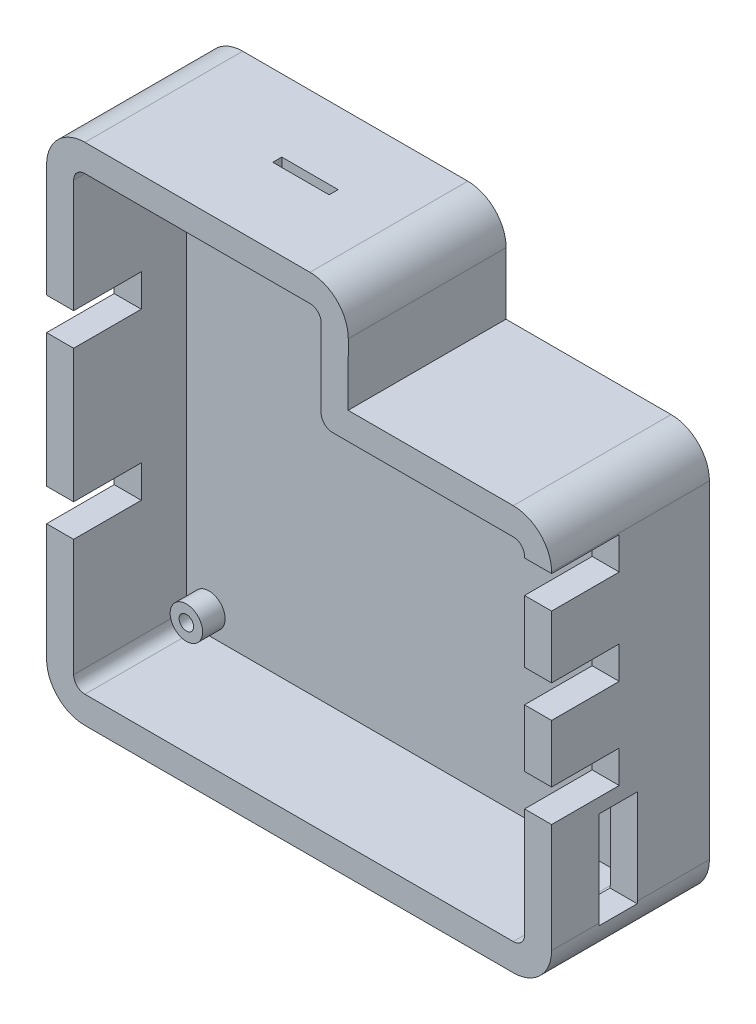
SolidWorks part; units mm, degrees
ref_plane "Front Plane" through (0, 0, 0) normal (0, 0, 1) x (1, 0, 0)
ref_plane "Top Plane" through (0, 0, 0) normal (0, 1, 0) x (1, 0, 0)
ref_plane "Right Plane" through (0, 0, 0) normal (1, 0, 0) x (0, 0, -1)
sketch "Sketch4" plane through (0, 0, 0) normal (0, 0, 1) x (1, 0, 0)
  line L0 (34.8872, 175.0129) -> (-15.0228, 175.0129)
  line L1 (-23.5228, 166.5129) -> (-23.5228, 71.5129)
  line L2 (-15.0228, 63.0129) -> (79.9772, 63.0129)
  line L3 (88.4772, 71.5129) -> (88.4772, 144.2329)
  line L4 (79.9772, 152.7329) -> (77.9872, 152.7329)
  line L5 (77.9872, 152.7329) -> (71.6372, 152.7329)
  line L6 (71.6372, 152.7329) -> (50.0472, 152.7329)
  line L7 (50.0472, 152.7329) -> (43.6972, 152.7329)
  line L8 (43.6972, 152.7329) -> (43.3553, 152.7329)
  line L9 (43.3553, 152.7329) -> (43.3872, 166.4932)
  line L20 (34.8872, 169.0129) -> (-15.0228, 169.0129)
  line L21 (-17.5228, 166.5129) -> (-17.5228, 71.5129)
  line L22 (-15.0228, 69.0129) -> (79.9772, 69.0129)
  line L23 (82.4772, 71.5129) -> (82.4772, 144.2329)
  line L24 (79.9772, 146.7329) -> (77.9872, 146.7329)
  line L25 (77.9872, 146.7329) -> (71.6372, 146.7329)
  line L26 (71.6372, 146.7329) -> (50.0472, 146.7329)
  line L27 (50.0472, 146.7329) -> (43.6972, 146.7329)
  line L28 (43.6972, 146.7329) -> (39.8872, 146.7329)
  line L29 (37.3472, 149.2729) -> (37.3872, 166.5071)
  arc A0 (-15.0228, 175.0129) -> (-23.5228, 166.5129) centre (-15.0228, 166.5129) ccw
  arc A1 (-23.5228, 71.5129) -> (-15.0228, 63.0129) centre (-15.0228, 71.5129) ccw
  circle A2 centre (-12.5228, 74.0129) radius 1.6
  arc A3 (79.9772, 63.0129) -> (88.4772, 71.5129) centre (79.9772, 71.5129) ccw
  circle A4 centre (68.8772, 74.8129) radius 1.6
  arc A5 (88.4772, 144.2329) -> (79.9772, 152.7329) centre (79.9772, 144.2329) ccw
  circle A6 centre (31.8772, 160.9129) radius 1.6
  arc A7 (43.3553, 152.7329) -> (43.3553, 152.7329) centre (43.3553, 152.7329) ccw
  circle A8 centre (-7.8228, 160.9129) radius 1.6
  arc A9 (43.3872, 166.4932) -> (34.8872, 175.0129) centre (34.8872, 166.5129) ccw
  arc A14 (-15.0228, 175.0129) -> (-23.5228, 166.5129) centre (-15.0228, 166.5129) ccw construction
  arc A20 (-15.0228, 169.0129) -> (-17.5228, 166.5129) centre (-15.0228, 166.5129) ccw
  arc A21 (-17.5228, 71.5129) -> (-15.0228, 69.0129) centre (-15.0228, 71.5129) ccw
  arc A22 (79.9772, 69.0129) -> (82.4772, 71.5129) centre (79.9772, 71.5129) ccw
  arc A23 (82.4772, 144.2329) -> (79.9772, 146.7329) centre (79.9772, 144.2329) ccw
  arc A24 (37.3472, 149.2729) -> (39.8872, 146.7329) centre (39.8872, 149.2729) ccw
  arc A25 (37.3872, 166.5071) -> (34.8872, 169.0129) centre (34.8872, 166.5129) ccw
  point P9 (39.8872, 146.7329)
  point P52 (0, 0)
  point P53 (0, 0)
  point P54 (-14.8357, 70.8386)
  point P55 (68.8772, 74.0129)
  point P56 (43.6972, 152.7329)
  point P57 (68.5766, 74.839)
  point P58 (-15.0228, 175.0129)
  point P59 (0, 0)
  dimension "D3" = 8.5
  dimension "D4" = 8.5
  dimension "D5" = 8.5
  dimension "D9" = 2.54
  dimension "D16" = 2.5
  dimension "D18" = 72.72
  dimension "D19" = 11.1
  dimension "D34" = 3.2
  dimension "D35" = 3.2
  dimension "D36" = 3.2
  dimension "D37" = 3.2
  dimension "D2" = 95
  dimension "D6" = 95
  dimension "D7" = 95
  dimension "D8" = 95
  dimension "D10" = 17.2342
  dimension "D11" = 3.81
  dimension "D12" = 6.35
  dimension "D13" = 21.59
  dimension "D14" = 6.35
  dimension "D15" = 1.99
  dimension "D17" = 72.72
  dimension "D20" = 11.1
  dimension "D21" = 2.5
  dimension "D22" = 2.5
  dimension "D23" = 5.6
  dimension "D24" = 7.2
  dimension "D25" = 5.6
  dimension "D26" = 3.01
  dimension "D27" = 74.8129
  dimension "D28" = 68.8772
  dimension "D29" = 270
  dimension "D30" = 77.72
  dimension "D31" = 112
  dimension "D32" = 112
  dimension "D33" = 0.133
  dimension "D1" = 6
extrude "Boss-Extrude1" add sketch "Sketch4" along normal blind 35 contours L9 A9 L0 A0 L1 A1 L2 A3 L3 A5 L4 L5 L6 L7 L8 A25 L29 A24 L28 L27 L26 L25 L24 A23 L23 A22 L22 A21 L21 A20 L20 region at (39.7833, 171.3976, 0)
extrude "Boss-Extrude2" add sketch "Sketch4<3>" along normal blind 10 contours L29 A25 L20 A20 L21 A21 L22 A22 L23 A23 L24 L25 L26 L27 L28 A24 A8 A6 A4 A2 region at (29.4425, 114.6581, 0)
sketch "Sketch4<3>" plane through (0, 0, 0) normal (0, 0, 1) x (1, 0, 0) same geometry as "Sketch4"
sketch "Sketch6" plane through (0, 0, 10) normal (0, 0, 1) x (1, 0, 0)
  circle A0 centre (68.8772, 74.8129) radius 3.6
  circle A1 centre (68.8772, 74.8129) radius 1.6 construction
  circle A2 centre (-12.5228, 74.0129) radius 3.6
  circle A3 centre (31.8772, 160.9129) radius 3.6
  circle A4 centre (-7.8228, 160.9129) radius 3.6
  circle A5 centre (31.8772, 160.9129) radius 1.6 construction
  circle A6 centre (-7.8228, 160.9129) radius 1.6 construction
  circle A7 centre (-12.5228, 74.0129) radius 1.6 construction
  dimension "D1" = 2
  dimension "D2" = 2
  dimension "D3" = 2
  dimension "D4" = 2
extrude "Boss-Extrude4" add sketch "Sketch6" along normal blind 5
sketch "Sketch10" plane through (0, 0, 10) normal (0, 0, 1) x (1, 0, 0)
  circle A0 centre (-7.8228, 160.9129) radius 1.6
  circle A1 centre (-12.5228, 74.0129) radius 1.6
  circle A2 centre (31.8772, 160.9129) radius 1.6
  circle A3 centre (68.8772, 74.8129) radius 1.6
extrude "Cut-Extrude3" cut sketch "Sketch10" against normal through all and the other way through all
sketch "Sketch11" plane through (88.4772, 0, 0) normal (1, 0, 0) x (0, 0, -1)
  line L1 (-15.9922, 71.0129) -> (-24.4922, 71.0129)
  line L2 (-15.9922, 71.0129) -> (-15.9922, 92.5129)
  line L3 (-15.9922, 92.5129) -> (-24.4922, 92.5129)
  line L4 (-24.4922, 71.0129) -> (-24.4922, 92.5129)
  dimension "D1" = 8.5
  dimension "D2" = 21.5
  dimension "D3" = 16
  dimension "D4" = 8
extrude "Cut-Extrude4" cut sketch "Sketch11" against normal up to next
sketch "Sketch12" plane through (0, 175.0129, 0) normal (0, 1, 0) x (1, 0, 0)
  line L1 (22.1372, -16) -> (9.6372, -16)
  line L2 (22.1372, -16) -> (22.1372, -18)
  line L3 (22.1372, -18) -> (9.6372, -18)
  line L4 (9.6372, -16) -> (9.6372, -18)
  line L5 (34.8872, 0) -> (-15.0228, 0) construction
  dimension "D1" = 15.25
  dimension "D2" = 16
  dimension "D3" = 2
  dimension "D4" = 12.5
extrude "Cut-Extrude5" cut sketch "Sketch12" against normal up to surface (6 mm away) up to face at (9.9322, 169.0129, 22.5)
sketch "Sketch13" plane through (0, 0, 35) normal (0, 0, 1) x (1, 0, 0)
  line L0 (82.4772, 71.5129) -> (82.4772, 144.2329) construction
  line L1 (82.4772, 136.7329) -> (88.4772, 136.7329)
  line L2 (82.4772, 136.7329) -> (82.4772, 143.9329)
  line L3 (82.4772, 143.9329) -> (88.4772, 143.9329)
  line L4 (88.4772, 136.7329) -> (88.4772, 143.9329)
  line L5 (88.4772, 71.5129) -> (88.4772, 144.2329) construction
  line L7 (82.4772, 122.9329) -> (88.4772, 122.9329)
  line L8 (82.4772, 122.9329) -> (82.4772, 115.7329)
  line L9 (82.4772, 115.7329) -> (88.4772, 115.7329)
  line L10 (88.4772, 122.9329) -> (88.4772, 115.7329)
  line L11 (82.4772, 102.9329) -> (88.4772, 102.9329)
  line L12 (82.4772, 102.9329) -> (82.4772, 95.7329)
  line L13 (82.4772, 95.7329) -> (88.4772, 95.7329)
  line L14 (88.4772, 102.9329) -> (88.4772, 95.7329)
  dimension "D1" = 2.8
  dimension "D2" = 7.2
  dimension "D3" = 7.2
  dimension "D4" = 7.2
  dimension "D5" = 13.8
  dimension "D6" = 12.8
extrude "Cut-Extrude6" cut sketch "Sketch13" against normal blind 15
sketch "Sketch14" plane through (0, 0, 35) normal (0, 0, 1) x (1, 0, 0)
  line L0 (-23.5228, 166.5129) -> (-23.5228, 71.5129) construction
  line L1 (-23.5228, 104.7129) -> (-17.5228, 104.7129)
  line L2 (-23.5228, 104.7129) -> (-23.5228, 97.5129)
  line L3 (-23.5228, 97.5129) -> (-17.5228, 97.5129)
  line L4 (-17.5228, 104.7129) -> (-17.5228, 97.5129)
  line L5 (-17.5228, 166.5129) -> (-17.5228, 71.5129) construction
  line L7 (-23.5228, 141.4129) -> (-17.5228, 141.4129)
  line L8 (-23.5228, 141.4129) -> (-23.5228, 134.2129)
  line L9 (-23.5228, 134.2129) -> (-17.5228, 134.2129)
  line L10 (-17.5228, 141.4129) -> (-17.5228, 134.2129)
  dimension "D1" = 26
  dimension "D2" = 7.2
  dimension "D3" = 7.2
  dimension "D4" = 29.5
extrude "Cut-Extrude7" cut sketch "Sketch14" against normal blind 15
